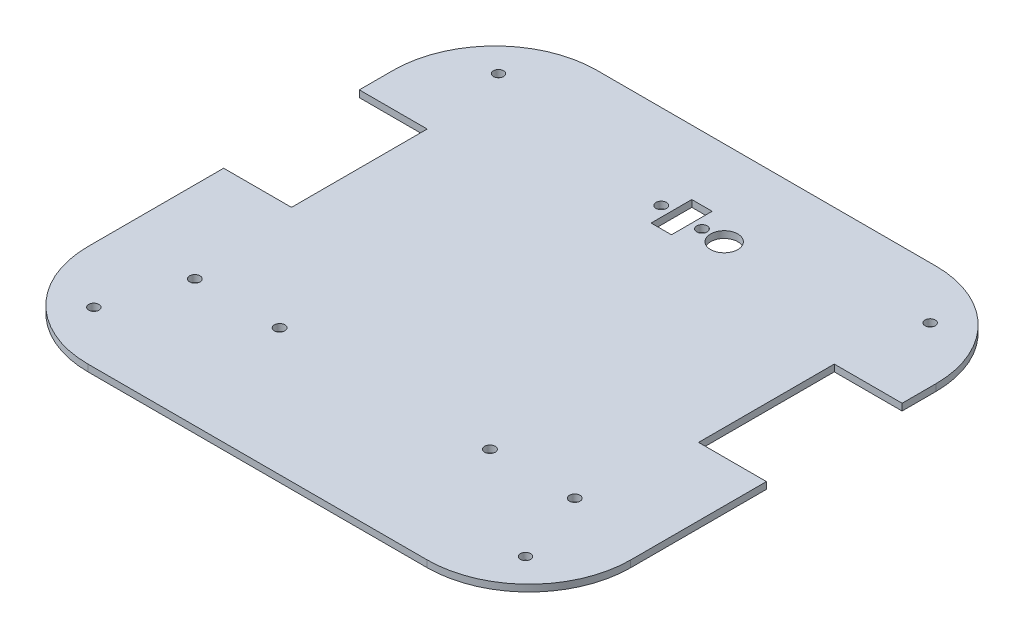
SolidWorks part; units mm, degrees
ref_plane "Front Plane" through (0, 0, 0) normal (0, 0, 1) x (1, 0, 0)
ref_plane "Top Plane" through (0, 0, 0) normal (0, 1, 0) x (1, 0, 0)
ref_plane "Right Plane" through (0, 0, 0) normal (1, 0, 0) x (0, 0, -1)
sketch "Sketch1" plane through (0, 0, 0) normal (0, 1, 0) x (1, 0, 0)
  line L0 (-80, 35) -> (-60, 35)
  line L1 (-50, -75) -> (50, -75)
  line L2 (-80, -45) -> (-80, -5)
  line L3 (-50, 75) -> (50, 75)
  line L4 (80, -45) -> (80, -5)
  line L5 (-80, -75) -> (80, 75) construction
  line L6 (-80, 75) -> (80, -75) construction
  line L7 (-60, 35) -> (-60, -5)
  line L8 (-60, -5) -> (-80, -5)
  line L9 (0, 75) -> (0, 0) construction
  line L10 (60, -5) -> (80, -5)
  line L11 (60, 35) -> (60, -5)
  line L12 (80, 35) -> (60, 35)
  line L13 (-80, 35) -> (-80, 45)
  line L14 (80, 35) -> (80, 45)
  line L15 (0, 0) -> (69.2486, 0) construction
  arc A0 (50, -75) -> (80, -45) centre (50, -45) ccw
  arc A1 (-50, -75) -> (-80, -45) centre (-50, -45) cw
  arc A2 (50, 75) -> (80, 45) centre (50, 45) cw
  arc A3 (-80, 45) -> (-50, 75) centre (-50, 45) cw
  circle A4 centre (-63.621, 59.6447) radius 1.5
  circle A5 centre (63.621, 59.6447) radius 1.5
  circle A6 centre (63.621, -59.6447) radius 1.5
  circle A7 centre (-63.621, -59.6447) radius 1.5
  point P0 (0, 0)
  dimension "D3" = 30
  dimension "D7" = 3
  dimension "D8" = 20
  dimension "D1" = 150
  dimension "D2" = 160
  dimension "D4" = 20
  dimension "D5" = 40
  dimension "D6" = 10
extrude "Boss-Extrude1" add sketch "Sketch1" along normal blind 2
sketch "Sketch2" plane through (0, 2, 0) normal (0, 1, 0) x (1, 0, 0)
  line L0 (-6, 50) -> (6, 50)
  line L1 (0, 75) -> (0, 25.7423) construction
  line L2 (-3, 44) -> (3, 44)
  line L3 (-3, 44) -> (-3, 56)
  line L4 (-3, 56) -> (3, 56)
  line L5 (3, 44) -> (3, 56)
  line L6 (-3, 44) -> (3, 56) construction
  line L7 (-3, 56) -> (3, 44) construction
  line L8 (50, 75) -> (-50, 75) construction
  line L9 (7.55, 50) -> (12.55, 50)
  circle A0 centre (-6, 50) radius 1.55
  circle A2 centre (6, 50) radius 1.55
  circle A3 centre (12.55, 50) radius 4
  point P4 (0, 50)
  dimension "D1" = 3.1
  dimension "D2" = 3.1
  dimension "D7" = 8
  dimension "D3" = 12
  dimension "D4" = 6
  dimension "D5" = 12
  dimension "D6" = 5
  dimension "D8" = 0
  dimension "D9" = 25
  dimension "D10" = 0
extrude "Cut-Extrude1" cut sketch "Sketch2" against normal blind 10 contours L0 L5 L4 L3 | L2 L5 L0 L3 | A0 | A2 | A3 region at (12.55, 2, -53.8869) region at (6, 2, -51.5062) region at (0, 2, -53) region at (0, 2, -47) region at (-7.5062, 2, -50)
sketch "Sketch3" plane through (0, 2, 0) normal (0, 1, 0) x (1, 0, 0)
  line L0 (0, 0) -> (0, -75) construction
  line L1 (-50, -75) -> (50, -75) construction
  line L2 (0, -37.5) -> (-62, -37.5) construction
  line L3 (0, -37.5) -> (62, -37.5) construction
  circle A0 centre (-56, -37.5) radius 1.55
  circle A1 centre (-31, -37.5) radius 1.55
  circle A2 centre (31, -37.5) radius 1.55
  circle A3 centre (56, -37.5) radius 1.55
  point P13 (-39.1553, -28.7334)
  dimension "D1" = 3.1
  dimension "D2" = 3.1
  dimension "D3" = 6
  dimension "D4" = 25
extrude "Cut-Extrude2" cut sketch "Sketch3" against normal blind 10
